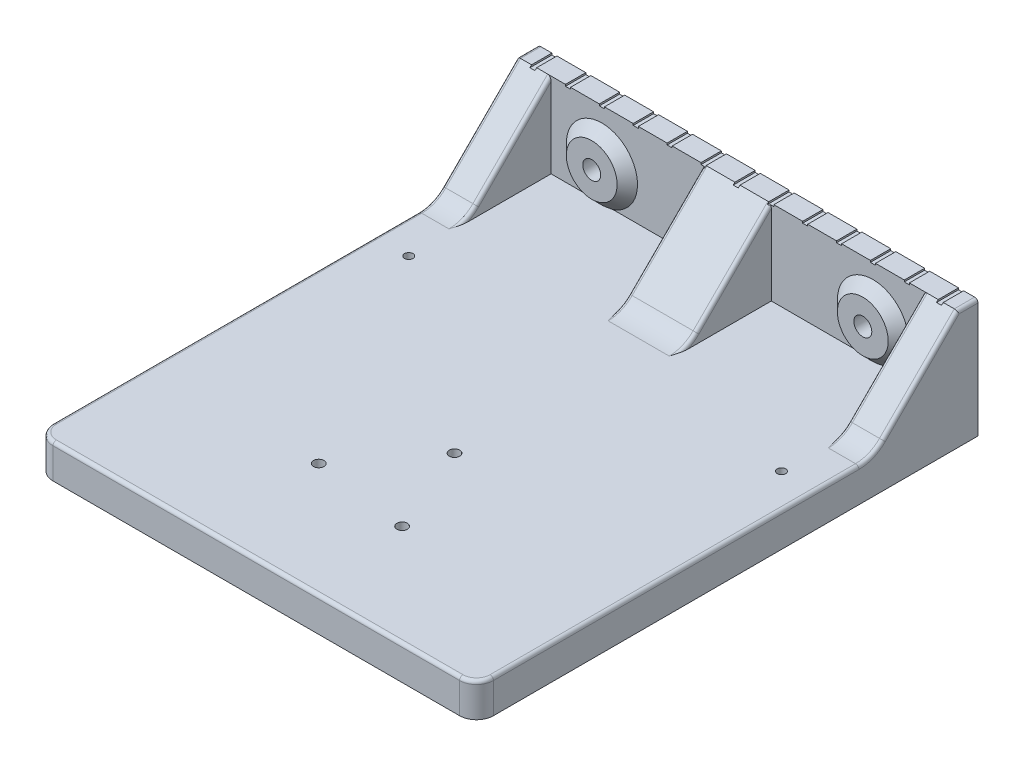
SolidWorks part; units mm, degrees
ref_plane "Ebene vorne" through (0, 0, 0) normal (0, 0, 1) x (1, 0, 0)
ref_plane "Ebene oben" through (0, 0, 0) normal (0, 1, 0) x (1, 0, 0)
ref_plane "Ebene rechts" through (0, 0, 0) normal (1, 0, 0) x (0, 0, -1)
sketch "Skizze1" plane through (0, 0, 0) normal (0, 1, 0) x (1, 0, 0)
  line L0 (0, 90.0641) -> (0, -83.7606) construction
  line L1 (-79.0807, 0) -> (85.5752, 0) construction
  line L2 (-65, -40) -> (-65, 0)
  line L4 (65, -40) -> (65, 0)
  line L5 (-65, -40) -> (65, -40)
  line L6 (-65, 0) -> (-65, 108)
  line L7 (-65, 108) -> (65, 108)
  line L8 (65, 0) -> (65, 108)
  point P9 (0, 40)
  point P10 (0, -40)
  point P12 (58.0434, 0)
  point P13 (-58.0434, 0)
  point P15 (0, 108)
  dimension "D1" = 40
  dimension "D2" = 108
  dimension "D3" = 130
extrude "Aufsatz-Linear austragen1" add sketch "Skizze1" along normal blind 10
ref_axis "Achse1" through (0, -0.5, 0) along (0, 1, 0)
sketch "Skizze2" plane through (0, 0, 0) normal (1, 0, 0) x (0, 0, -1)
  line L0 (108, 10) -> (108, 35)
  line L1 (102, 35) -> (77, 10)
  line L2 (77, 10) -> (108, 10)
  line L3 (108, 10) -> (-40, 10) construction
  line L4 (108, 10) -> (108, 0) construction
  line L5 (108, 35) -> (102, 35)
  line L6 (108, 0) -> (-40, 0) construction
  dimension "D1" = 35
  dimension "D2" = 45
  dimension "D3" = 6
extrude "Aufsatz-Linear austragen2" add sketch "Skizze2" along normal up to surface and the other way up to surface up to face at (65, 5, -34) other way up to face at (-65, 5, -34)
ref_plane "Ebene1" through (10, 0, 0) normal (1, 0, 0) x (0, 0, -1)
sketch "Skizze3" plane through (10, 0, 0) normal (1, 0, 0) x (0, 0, -1)
  line L0 (102, 35) -> (102, 10)
  line L1 (102, 10) -> (77, 10)
  line L2 (77, 10) -> (102, 35)
  line L3 (77, 10) -> (-40, 10) construction
  line L4 (77, 10) -> (102, 35) construction
  dimension "D1" = 25
extrude "Schnitt-Linear austragen1" cut sketch "Skizze3" along normal offset from surface (45 mm away) 10 up to face at (65, 15, -52.5)
ref_plane "Ebene2" through (-10, 0, 0) normal (1, 0, 0) x (0, 0, -1)
sketch "Skizze4" plane through (-10, 0, 0) normal (1, 0, 0) x (0, 0, -1)
  line L0 (102, 35) -> (102, 10)
  line L1 (102, 10) -> (77, 10)
  line L2 (77, 10) -> (102, 35)
extrude "Schnitt-Linear austragen2" cut sketch "Skizze4" against normal offset from surface (45 mm away) 10 up to face at (-65, 15, -52.5)
sketch "Skizze5" plane through (0, 0, -108) normal (0, 0, -1) x (-1, 0, 0)
  line L0 (-110.8516, 20) -> (91.1215, 20) construction
  line L1 (0, 64.4473) -> (0, -38.7839) construction
  line L2 (82.5, 0) -> (-82.5, 0) construction
  line L3 (0, 19.25) -> (0, -19.25) construction
  line L4 (-50, 16) -> (-30, 16)
  line L5 (-50, 16) -> (-50, 24)
  line L6 (-50, 24) -> (-30, 24)
  line L7 (-30, 16) -> (-30, 24)
  line L8 (-50, 16) -> (-30, 24) construction
  line L9 (-50, 24) -> (-30, 16) construction
  line L10 (30, 16) -> (30, 24)
  line L11 (50, 16) -> (30, 16)
  line L12 (50, 16) -> (50, 24)
  line L13 (50, 24) -> (30, 24)
  point P8 (-40, 20)
  dimension "D1" = 20
  dimension "D2" = 8
  dimension "D3" = 20
  dimension "D4" = 40
extrude "Aufsatz-Linear austragen3" add sketch "Skizze5" along normal blind 2.5
sketch "Skizze6" plane through (0, 0, -110.5) normal (0, 0, -1) x (-1, 0, 0)
  line L2 (0, 69.7735) -> (0, -44.034) construction
  circle A0 centre (-40, 20) radius 2.65
  circle A1 centre (40, 20) radius 2.65
  dimension "D1" = 5.3
extrude "Schnitt-Linear austragen3" cut sketch "Skizze6" against normal through all
fillet "Verrundung1" radius 10 3 edges at (60, 10, -77) (0, 10, -77) (-60, 10, -77)
fillet "Verrundung2" radius 5 2 edges at (65, 5, 40) (-65, 5, 40)
sketch "Skizze7" plane through (0, 0, 0) normal (0, -1, 0) x (1, 0, 0)
  line L0 (0, 33.4621) -> (0, -33.3373) construction
  line L1 (-37.4784, 0) -> (30.7588, 0) construction
  line L2 (0, 0) -> (-31.3552, 12.9878) construction
  line L3 (2.1537, -16.3588) -> (0, 0) construction
  line L4 (13.0903, 10.0446) -> (0, 0) construction
  circle A0 centre (0, 0) radius 16.5 construction
  circle A1 centre (-15.244, 6.3143) radius 1.55
  circle A2 centre (13.0903, 10.0446) radius 1.55
  circle A3 centre (2.1537, -16.3588) radius 1.55
  dimension "D2" = 33
  dimension "D3" = 3.1
  dimension "D1" = 22.5
  dimension "D4" = 120
  dimension "D5" = 120
extrude "Schnitt-Linear austragen4" cut sketch "Skizze7" against normal up to next
sketch "Skizze8" plane through (0, 0, 0) normal (0, -1, 0) x (1, 0, 0)
  circle A0 centre (2.1537, -16.3588) radius 2.85
  circle A1 centre (13.0903, 10.0446) radius 2.85
  circle A2 centre (-15.244, 6.3143) radius 2.85
  dimension "D1" = 5.7
extrude "Schnitt-Linear austragen5" cut sketch "Skizze8" against normal offset from surface (3.2 mm away) 6.8 up to face at (-15.244, 10, 4.7643)
sketch "Skizze9" plane through (0, 35, 0) normal (0, 1, 0) x (1, 0, 0)
  line L0 (0, 138.9035) -> (0, -30.1784) construction
  line L1 (0.75, 108) -> (-0.75, 108)
  line L2 (-0.75, 108) -> (-0.75, 98)
  line L3 (10, 102) -> (-10, 102) construction
  line L4 (-0.75, 98) -> (0.75, 98)
  line L5 (65, 108) -> (-65, 108) construction
  line L6 (0.75, 108) -> (0.75, 98)
  point P12 (0, 102)
  point P13 (0, 108)
  dimension "D1" = 1.5
  dimension "D2" = 10
extrude "Schnitt-Linear austragen6" cut sketch "Skizze9" against normal blind 0.5
ref_axis "Achse2" through (82.5, 0, 0) along (-1, 0, 0)
pattern_linear "Lineares Muster1" count 8 spacing 10 along (1, 0, 0) of "Schnitt-Linear austragen6"
pattern_linear "Lineares Muster2" count 8 spacing 10 along (-1, 0, 0) of "Schnitt-Linear austragen6"
fillet "Verrundung3" radius 1 19 edges at (-55, 10.7612, -76.6847) (-10, 10.7612, -76.6847) (10, 10.7612, -76.6847) (55, 10.7612, -76.6847) (-65, 23.9645, -90.9645) (-65, 10.7612, -76.6847) (-65, 10, -18.9289) (-63.5355, 10, 38.5355) (65, 23.9645, -90.9645) (65, 10.7612, -76.6847) (65, 10, -18.9289) (63.5355, 10, 38.5355) (-55, 23.9645, -90.9645) (-10, 23.7145, -90.7145) (10, 23.7145, -90.7145) (55, 23.9645, -90.9645) (65, 35, -105) (-65, 35, -105) (0, 10, 40)
sketch "Skizze10" plane through (0, 0, -102) normal (0, 0, 1) x (1, 0, 0)
  line L0 (0, 50.8683) -> (0, -26.14) construction
  circle A0 centre (-40, 20) radius 7.5
  circle A1 centre (40, 20) radius 7.5
  circle A2 centre (-40, 20) radius 2.65
  circle A3 centre (-40, 20) radius 2.65 construction
  circle A4 centre (40, 20) radius 2.65
  dimension "D1" = 15
extrude "Aufsatz-Linear austragen4" add sketch "Skizze10" along normal blind 3
chamfer "Fase1" distance 3 angle 45 2 edges at (32.5, 20, -102) (-47.5, 20, -102)
sketch "Skizze11" plane through (0, 0, 0) normal (0, 1, 0) x (1, 0, 0)
  line L0 (0, 140.9895) -> (0, -68.9864) construction
  line L1 (-122.8389, 0) -> (124.0058, 0) construction
  circle A0 centre (-55, 60) radius 1.25
  circle A1 centre (55, 60) radius 1.25
  dimension "D1" = 2.5
  dimension "D2" = 110
  dimension "D3" = 60
extrude "Schnitt-Linear austragen8" cut sketch "Skizze11" along normal through all
ref_axis "Achse3" through (-71.5, 0, 0) along (1, 0, 0)
ref_axis "Achse4" through (0, 0, -118.025) along (0, 0, 1)
ref_axis "Achse5" through (0, 36.75, 0) along (0, -1, 0)
